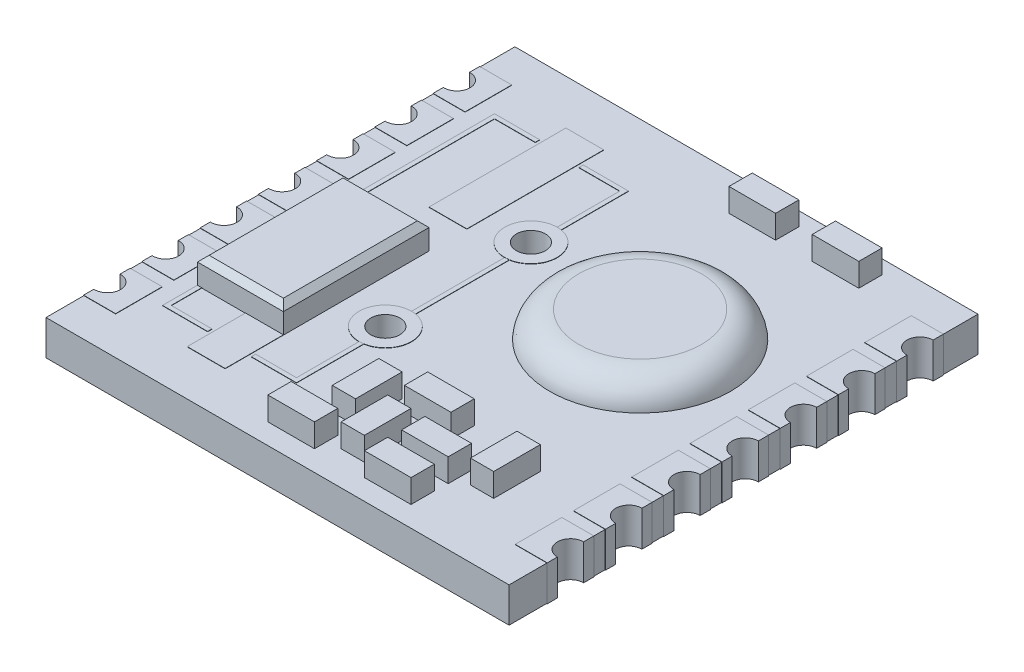
SolidWorks part; units mm, degrees
ref_plane "Vorne" through (0, 0, 0) normal (0, 0, 1) x (1, 0, 0)
ref_plane "Oben" through (0, 0, 0) normal (0, 1, 0) x (1, 0, 0)
ref_plane "Rechts" through (0, 0, 0) normal (1, 0, 0) x (0, 0, -1)
sketch "Skizze1" plane through (0, 0, 0) normal (0, 0, 1) x (1, 0, 0)
  line L1 (0, 0) -> (15.9, 0)
  line L2 (0, 0) -> (0, 1.2)
  line L3 (0, 1.2) -> (15.9, 1.2)
  line L4 (15.9, 0) -> (15.9, 1.2)
  dimension "D1" = 1.2
  dimension "D2" = 15.9
extrude "Linear austragen1" add sketch "Skizze1" along normal blind 16.1
sketch "Skizze3" plane through (15.9, 0, 0) normal (1, 0, 0) x (0, 0, -1)
  line L0 (-16.1, 1.2) -> (0, 1.2) construction
  line L1 (-14.8, 1.2) -> (-13.2, 1.2)
  line L2 (-14.8, 1.2) -> (-14.8, 0)
  line L3 (-14.8, 0) -> (-13.2, 0)
  line L4 (-13.2, 1.2) -> (-13.2, 0)
  line L5 (-16.1, 0) -> (0, 0) construction
  line L6 (-16.1, 0) -> (-16.1, 1.2) construction
  line L7 (-12.8, 1.2) -> (-11.2, 1.2)
  line L8 (-12.8, 1.2) -> (-12.8, 0)
  line L9 (-12.8, 0) -> (-11.2, 0)
  line L10 (-11.2, 1.2) -> (-11.2, 0)
  line L11 (-10.8, 1.2) -> (-9.2, 1.2)
  line L12 (-10.8, 1.2) -> (-10.8, 0)
  line L13 (-10.8, 0) -> (-9.2, 0)
  line L14 (-9.2, 1.2) -> (-9.2, 0)
  line L15 (-8.8, 1.2) -> (-7.2, 1.2)
  line L16 (-8.8, 1.2) -> (-8.8, 0)
  line L17 (-8.8, 0) -> (-7.2, 0)
  line L18 (-7.2, 1.2) -> (-7.2, 0)
  line L19 (-6.8, 1.2) -> (-5.2, 1.2)
  line L20 (-6.8, 1.2) -> (-6.8, 0)
  line L21 (-6.8, 0) -> (-5.2, 0)
  line L22 (-5.2, 1.2) -> (-5.2, 0)
  line L23 (-4.8, 1.2) -> (-3.2, 1.2)
  line L24 (-4.8, 1.2) -> (-4.8, 0)
  line L25 (-4.8, 0) -> (-3.2, 0)
  line L26 (-3.2, 1.2) -> (-3.2, 0)
  line L27 (-2.8, 1.2) -> (-1.2, 1.2)
  line L28 (-2.8, 1.2) -> (-2.8, 0)
  line L29 (-2.8, 0) -> (-1.2, 0)
  line L30 (-1.2, 1.2) -> (-1.2, 0)
  dimension "D1" = 1.6
  dimension "D2" = 1.6
  dimension "D3" = 1.6
  dimension "D4" = 1.3
  dimension "D5" = 0.4
  dimension "D6" = 0.4
  dimension "D7" = 0.4
  dimension "D8" = 0.4
  dimension "D9" = 0.4
  dimension "D10" = 0.4
  dimension "D11" = 1.6
  dimension "D12" = 1.6
  dimension "D13" = 1.6
  dimension "D14" = 1.6
sketch "Skizze4" plane through (0, 0, 0) normal (-1, 0, 0) x (0, 0, 1)
  line L0 (16.1, 1.2) -> (0, 1.2) construction
  line L1 (14.8, 1.2) -> (13.2, 1.2)
  line L2 (14.8, 1.2) -> (14.8, 0)
  line L3 (14.8, 0) -> (13.2, 0)
  line L4 (13.2, 1.2) -> (13.2, 0)
  line L5 (16.1, 0) -> (0, 0) construction
  line L6 (16.1, 1.2) -> (16.1, 0) construction
  line L7 (12.8, 1.2) -> (11.2, 1.2)
  line L8 (12.8, 1.2) -> (12.8, 0)
  line L9 (12.8, 0) -> (11.2, 0)
  line L10 (11.2, 1.2) -> (11.2, 0)
  line L11 (10.8, 1.2) -> (9.2, 1.2)
  line L12 (10.8, 1.2) -> (10.8, 0)
  line L13 (10.8, 0) -> (9.2, 0)
  line L14 (9.2, 1.2) -> (9.2, 0)
  line L15 (8.8, 1.2) -> (7.2, 1.2)
  line L16 (8.8, 1.2) -> (8.8, 0)
  line L17 (8.8, 0) -> (7.2, 0)
  line L18 (7.2, 1.2) -> (7.2, 0)
  line L23 (6.8, 1.2) -> (5.2, 1.2)
  line L24 (6.8, 1.2) -> (6.8, 0)
  line L25 (6.8, 0) -> (5.2, 0)
  line L26 (5.2, 1.2) -> (5.2, 0)
  line L27 (4.8, 1.2) -> (3.2, 1.2)
  line L28 (4.8, 1.2) -> (4.8, 0)
  line L29 (4.8, 0) -> (3.2, 0)
  line L30 (3.2, 1.2) -> (3.2, 0)
  line L31 (2.8, 1.2) -> (1.2, 1.2)
  line L32 (2.8, 1.2) -> (2.8, 0)
  line L33 (2.8, 0) -> (1.2, 0)
  line L34 (1.2, 1.2) -> (1.2, 0)
  dimension "D1" = 0.4
  dimension "D2" = 0.4
  dimension "D3" = 0.4
  dimension "D4" = 0.4
  dimension "D5" = 0.4
  dimension "D6" = 0.4
  dimension "D7" = 1.3
  dimension "D8" = 1.6
  dimension "D9" = 1.6
  dimension "D10" = 1.6
  dimension "D11" = 1.6
  dimension "D12" = 1.6
  dimension "D13" = 1.6
  dimension "D14" = 1.6
extrude "Linear austragen2" add sketch "Skizze4" along normal blind 0.01
extrude "Linear austragen3" add sketch "Skizze3" along normal blind 0.01
sketch "Skizze5" plane through (0, 1.2, 0) normal (0, 1, 0) x (-1, 0, 0)
  line L1 (-15.91, 1.2) -> (-14.81, 1.2)
  line L2 (-15.91, 1.2) -> (-15.91, 2.8)
  line L3 (-15.91, 2.8) -> (-14.81, 2.8)
  line L4 (-14.81, 1.2) -> (-14.81, 2.8)
  line L5 (-15.91, 3.2) -> (-14.81, 3.2)
  line L6 (-15.91, 3.2) -> (-15.91, 4.8)
  line L7 (-15.91, 4.8) -> (-14.81, 4.8)
  line L8 (-14.81, 3.2) -> (-14.81, 4.8)
  line L9 (-15.91, 7.2) -> (-14.81, 7.2)
  line L10 (-15.91, 7.2) -> (-15.91, 8.8)
  line L11 (-15.91, 8.8) -> (-14.81, 8.8)
  line L12 (-14.81, 7.2) -> (-14.81, 8.8)
  line L13 (-15.91, 9.2) -> (-14.81, 9.2)
  line L14 (-15.91, 9.2) -> (-15.91, 10.8)
  line L15 (-15.91, 10.8) -> (-14.81, 10.8)
  line L16 (-14.81, 9.2) -> (-14.81, 10.8)
  line L17 (-15.91, 11.2) -> (-14.81, 11.2)
  line L18 (-15.91, 11.2) -> (-15.91, 12.8)
  line L19 (-15.91, 12.8) -> (-14.81, 12.8)
  line L20 (-14.81, 11.2) -> (-14.81, 12.8)
  line L21 (-15.91, 13.2) -> (-14.81, 13.2)
  line L22 (-15.91, 13.2) -> (-15.91, 14.8)
  line L23 (-15.91, 14.8) -> (-14.81, 14.8)
  line L24 (-14.81, 13.2) -> (-14.81, 14.8)
  line L25 (-15.91, 5.2) -> (-14.81, 5.2)
  line L26 (-15.91, 5.2) -> (-15.91, 6.8)
  line L27 (-15.91, 6.8) -> (-14.81, 6.8)
  line L28 (-14.81, 5.2) -> (-14.81, 6.8)
  line L29 (0.01, 1.2) -> (-1.09, 1.2)
  line L30 (0.01, 1.2) -> (0.01, 2.8)
  line L31 (0.01, 2.8) -> (-1.09, 2.8)
  line L32 (-1.09, 1.2) -> (-1.09, 2.8)
  line L33 (0.01, 3.2) -> (-1.09, 3.2)
  line L34 (0.01, 3.2) -> (0.01, 4.8)
  line L35 (0.01, 4.8) -> (-1.09, 4.8)
  line L36 (-1.09, 3.2) -> (-1.09, 4.8)
  line L37 (0.01, 5.2) -> (-1.09, 5.2)
  line L38 (0.01, 5.2) -> (0.01, 6.8)
  line L39 (0.01, 6.8) -> (-1.09, 6.8)
  line L40 (-1.09, 5.2) -> (-1.09, 6.8)
  line L41 (0.01, 7.2) -> (-1.09, 7.2)
  line L42 (0.01, 7.2) -> (0.01, 8.8)
  line L43 (0.01, 8.8) -> (-1.09, 8.8)
  line L44 (-1.09, 7.2) -> (-1.09, 8.8)
  line L45 (0.01, 9.2) -> (-1.09, 9.2)
  line L46 (0.01, 9.2) -> (0.01, 10.8)
  line L47 (0.01, 10.8) -> (-1.09, 10.8)
  line L48 (-1.09, 9.2) -> (-1.09, 10.8)
  line L49 (0.01, 11.2) -> (-1.09, 11.2)
  line L50 (0.01, 11.2) -> (0.01, 12.8)
  line L51 (0.01, 12.8) -> (-1.09, 12.8)
  line L52 (-1.09, 11.2) -> (-1.09, 12.8)
  line L53 (0.01, 13.2) -> (-1.09, 13.2)
  line L54 (0.01, 13.2) -> (0.01, 14.8)
  line L55 (0.01, 14.8) -> (-1.09, 14.8)
  line L56 (-1.09, 13.2) -> (-1.09, 14.8)
  dimension "D1" = 1.6
  dimension "D2" = 1.6
  dimension "D3" = 1.6
  dimension "D4" = 1.6
  dimension "D5" = 1.6
  dimension "D6" = 1.6
  dimension "D7" = 1.6
  dimension "D8" = 1.1
  dimension "D9" = 1.1
  dimension "D10" = 1.1
  dimension "D11" = 1.1
  dimension "D12" = 1.1
  dimension "D13" = 1.1
  dimension "D14" = 1.1
  dimension "D15" = 1.6
  dimension "D16" = 1.6
  dimension "D17" = 1.6
  dimension "D18" = 1.6
  dimension "D19" = 1.6
  dimension "D20" = 1.6
  dimension "D21" = 1.6
  dimension "D22" = 1.1
  dimension "D23" = 1.1
  dimension "D24" = 1.1
  dimension "D25" = 1.1
  dimension "D26" = 1.1
  dimension "D27" = 1.1
  dimension "D28" = 1.1
extrude "Linear austragen4" add sketch "Skizze5" along normal blind 0.01
sketch "Skizze6" plane through (0, 0, 0) normal (0, -1, 0) x (1, 0, 0)
  line L1 (15.91, 14.8) -> (14.81, 14.8)
  line L2 (15.91, 14.8) -> (15.91, 13.2)
  line L3 (15.91, 13.2) -> (14.81, 13.2)
  line L4 (14.81, 14.8) -> (14.81, 13.2)
  line L5 (15.91, 12.8) -> (14.81, 12.8)
  line L6 (15.91, 12.8) -> (15.91, 11.2)
  line L7 (15.91, 11.2) -> (14.81, 11.2)
  line L8 (14.81, 12.8) -> (14.81, 11.2)
  line L9 (15.91, 10.8) -> (14.81, 10.8)
  line L10 (15.91, 10.8) -> (15.91, 9.2)
  line L11 (15.91, 9.2) -> (14.81, 9.2)
  line L12 (14.81, 10.8) -> (14.81, 9.2)
  line L13 (15.91, 8.8) -> (14.81, 8.8)
  line L14 (15.91, 8.8) -> (15.91, 7.2)
  line L15 (15.91, 7.2) -> (14.81, 7.2)
  line L16 (14.81, 8.8) -> (14.81, 7.2)
  line L17 (15.91, 6.8) -> (14.81, 6.8)
  line L18 (15.91, 6.8) -> (15.91, 5.2)
  line L19 (15.91, 5.2) -> (14.81, 5.2)
  line L20 (14.81, 6.8) -> (14.81, 5.2)
  line L21 (15.91, 4.8) -> (14.81, 4.8)
  line L22 (15.91, 4.8) -> (15.91, 3.2)
  line L23 (15.91, 3.2) -> (14.81, 3.2)
  line L24 (14.81, 4.8) -> (14.81, 3.2)
  line L25 (15.91, 2.8) -> (14.81, 2.8)
  line L26 (15.91, 2.8) -> (15.91, 1.2)
  line L27 (15.91, 1.2) -> (14.81, 1.2)
  line L28 (14.81, 2.8) -> (14.81, 1.2)
  line L29 (-0.01, 14.8) -> (1.09, 14.8)
  line L30 (-0.01, 14.8) -> (-0.01, 13.2)
  line L31 (-0.01, 13.2) -> (1.09, 13.2)
  line L32 (1.09, 14.8) -> (1.09, 13.2)
  line L33 (-0.01, 12.8) -> (1.09, 12.8)
  line L34 (-0.01, 12.8) -> (-0.01, 11.2)
  line L35 (-0.01, 11.2) -> (1.09, 11.2)
  line L36 (1.09, 12.8) -> (1.09, 11.2)
  line L37 (-0.01, 10.8) -> (1.09, 10.8)
  line L38 (-0.01, 10.8) -> (-0.01, 9.2)
  line L39 (-0.01, 9.2) -> (1.09, 9.2)
  line L40 (1.09, 10.8) -> (1.09, 9.2)
  line L41 (-0.01, 8.8) -> (1.09, 8.8)
  line L42 (-0.01, 8.8) -> (-0.01, 7.2)
  line L43 (-0.01, 7.2) -> (1.09, 7.2)
  line L44 (1.09, 8.8) -> (1.09, 7.2)
  line L45 (-0.01, 6.8) -> (1.09, 6.8)
  line L46 (-0.01, 6.8) -> (-0.01, 5.2)
  line L47 (-0.01, 5.2) -> (1.09, 5.2)
  line L48 (1.09, 6.8) -> (1.09, 5.2)
  line L49 (-0.01, 4.8) -> (1.09, 4.8)
  line L50 (-0.01, 4.8) -> (-0.01, 3.2)
  line L51 (-0.01, 3.2) -> (1.09, 3.2)
  line L52 (1.09, 4.8) -> (1.09, 3.2)
  line L53 (-0.01, 2.8) -> (1.09, 2.8)
  line L54 (-0.01, 2.8) -> (-0.01, 1.2)
  line L55 (-0.01, 1.2) -> (1.09, 1.2)
  line L56 (1.09, 2.8) -> (1.09, 1.2)
  dimension "D1" = 1.6
  dimension "D2" = 1.6
  dimension "D3" = 1.6
  dimension "D4" = 1.6
  dimension "D5" = 1.6
  dimension "D6" = 1.6
  dimension "D7" = 1.6
  dimension "D8" = 1.1
  dimension "D9" = 1.1
  dimension "D10" = 1.1
  dimension "D11" = 1.1
  dimension "D12" = 1.1
  dimension "D13" = 1.1
  dimension "D14" = 1.1
  dimension "D15" = 1.6
  dimension "D16" = 1.6
  dimension "D17" = 1.6
  dimension "D18" = 1.6
  dimension "D19" = 1.6
  dimension "D20" = 1.6
  dimension "D21" = 1.6
  dimension "D22" = 1.1
  dimension "D23" = 1.1
  dimension "D24" = 1.1
  dimension "D25" = 1.1
  dimension "D26" = 1.1
  dimension "D27" = 1.1
  dimension "D28" = 1.1
extrude "Linear austragen5" add sketch "Skizze6" along normal blind 0.01
sketch "Skizze7" plane through (0, 1.21, 0) normal (0, 1, 0) x (-1, 0, 0)
  line L0 (-15.91, 2.8) -> (-15.91, 1.2) construction
  line L1 (-15.91, 1.2) -> (-14.81, 1.2) construction
  line L2 (-15.91, 2) -> (-0.01, 2) construction
  line L3 (-15.91, 2) -> (-15.91, 4) construction
  circle A0 centre (-15.91, 2) radius 0.45
  circle A1 centre (-0.01, 2) radius 0.45
  circle A2 centre (-15.91, 4) radius 0.45
  circle A3 centre (-0.01, 4) radius 0.45
  circle A4 centre (-15.91, 6) radius 0.45
  circle A5 centre (-0.01, 6) radius 0.45
  circle A6 centre (-15.91, 8) radius 0.45
  circle A7 centre (-0.01, 8) radius 0.45
  circle A8 centre (-15.91, 10) radius 0.45
  circle A9 centre (-0.01, 10) radius 0.45
  circle A10 centre (-15.91, 12) radius 0.45
  circle A11 centre (-0.01, 12) radius 0.45
  circle A12 centre (-15.91, 14) radius 0.45
  circle A13 centre (-0.01, 14) radius 0.45
  dimension "D2" = 0.9
  dimension "D1" = 0.8
  dimension "D3" = 90
extrude "Schnitt-Linear austragen2" cut sketch "Skizze7" against normal blind 2
sketch "Skizze8" plane through (0, 1.2, 0) normal (0, 1, 0) x (-1, 0, 0)
  line L0 (-15.9, 5.2) -> (-15.9, 4.8) construction
  line L1 (-15.9, 0) -> (0, 0) construction
  circle A0 centre (-10.85, 6.55) radius 3.1
  dimension "D2" = 6.2
  dimension "D1" = 5.05
  dimension "D3" = 6.55
extrude "Linear austragen6" add sketch "Skizze8" along normal blind 0.9
fillet "Verrundung1" radius 1 1 edges at (7.75, 2.1, 6.55)
sketch "Skizze9" plane through (0, 1.2, 0) normal (0, 1, 0) x (-1, 0, 0)
  line L0 (0, 1.2) -> (0, 0) construction
  line L1 (-1.65, 2.35) -> (-3.2, 2.35)
  line L2 (-1.65, 2.35) -> (-1.65, 13.75)
  line L3 (-1.65, 13.75) -> (-3.2, 13.75)
  line L4 (-6.25, 2.35) -> (-6.25, 13.75)
  line L5 (-15.9, 0) -> (0, 0) construction
  line L6 (-3.2, 2.35) -> (-3.2, 2.5)
  line L7 (-1.8, 2.5) -> (-3.2, 2.5)
  line L8 (-1.8, 2.5) -> (-1.8, 13.6)
  line L9 (-1.8, 13.6) -> (-3.2, 13.6)
  line L10 (-6.1, 2.5) -> (-6.1, 13.6)
  line L11 (-4.7, 2.35) -> (-4.7, 2.5)
  line L12 (-4.7, 2.35) -> (-6.25, 2.35)
  line L13 (-4.7, 2.5) -> (-6.1, 2.5)
  line L14 (-3.2, 13.6) -> (-3.2, 13.75)
  line L15 (-4.7, 13.6) -> (-4.7, 13.75)
  line L16 (-4.7, 13.6) -> (-6.1, 13.6)
  line L17 (-4.7, 13.75) -> (-6.25, 13.75)
  dimension "D1" = 4.6
  dimension "D2" = 11.4
  dimension "D3" = 6.25
  dimension "D4" = 2.35
  dimension "D5" = 0.15
  dimension "D6" = 0.15
  dimension "D7" = 0.15
  dimension "D8" = 0.15
  dimension "D9" = 1.55
  dimension "D10" = 1.55
extrude "Linear austragen7" add sketch "Skizze9" along normal blind 0.01
sketch "Skizze10" plane through (0, 1.2, 0) normal (0, 1, 0) x (-1, 0, 0)
  line L0 (-6.1, 2.5) -> (-6.1, 13.6) construction
  line L1 (-15.9, 0) -> (0, 0) construction
  circle A0 centre (-6.1, 5.55) radius 0.9
  circle A1 centre (-6.1, 10.55) radius 0.9
  dimension "D3" = 1.8
  dimension "D4" = 1.8
  dimension "D1" = 5
  dimension "D2" = 5.55
extrude "Linear austragen9" add sketch "Skizze10" along normal blind 0.011
sketch "Skizze11" plane through (0, 1.211, 0) normal (0, 1, 0) x (-1, 0, 0)
  circle A0 centre (-6.1, 10.55) radius 0.5
  circle A1 centre (-6.1, 5.55) radius 0.5
  dimension "D1" = 1
  dimension "D2" = 1
extrude "Schnitt-Linear austragen3" cut sketch "Skizze11" against normal blind 2
sketch "Skizze12" plane through (0, 1.2, 0) normal (0, 1, 0) x (-1, 0, 0)
  line L1 (-3.3, 1.55) -> (-4.6, 1.55)
  line L2 (-3.3, 1.55) -> (-3.3, 6.25)
  line L3 (-3.3, 14.55) -> (-4.6, 14.55)
  line L4 (-4.6, 1.55) -> (-4.6, 6.25)
  line L5 (-4.7, 2.35) -> (-4.7, 2.5) construction
  line L6 (-6.25, 2.35) -> (-4.7, 2.35) construction
  line L7 (-4.7, 13.75) -> (-6.25, 13.75) construction
  line L8 (-3.3, 6.25) -> (-4.6, 6.25)
  line L9 (-3.3, 9.85) -> (-4.6, 9.85)
  line L10 (-4.6, 9.85) -> (-4.6, 14.55)
  line L11 (-3.3, 9.85) -> (-3.3, 14.55)
  dimension "D1" = 1.3
  dimension "D2" = 0.1
  dimension "D3" = 0.8
  dimension "D4" = 0.8
  dimension "D5" = 4.7
  dimension "D6" = 4.7
extrude "Linear austragen10" add sketch "Skizze12" along normal blind 0.01
sketch "Skizze13" plane through (0, 1.2, 0) normal (0, 1, 0) x (-1, 0, 0)
  line L0 (-1.65, 2.35) -> (-1.65, 13.75) construction
  line L1 (-1.65, 7.55) -> (-4.6, 7.55)
  line L2 (-1.65, 7.55) -> (-1.65, 12.55)
  line L3 (-1.65, 12.55) -> (-4.6, 12.55)
  line L4 (-4.6, 7.55) -> (-4.6, 12.55)
  line L5 (-4.6, 14.55) -> (-4.6, 9.85) construction
  line L6 (-3.3, 6.25) -> (-4.6, 6.25) construction
  dimension "D1" = 1.3
  dimension "D2" = 5
extrude "Linear austragen11" add sketch "Skizze13" along normal blind 0.9
chamfer "Fase1" distance 0.2 angle 45 4 edges at (1.65, 2.1, 10.05) (3.125, 2.1, 12.55) (3.125, 2.1, 7.55) (4.6, 2.1, 10.05)
sketch "Skizze14" plane through (0, 1.2, 0) normal (0, 1, 0) x (-1, 0, 0)
  line L0 (-11.4841, 0.4772) -> (-13.0841, 0.4772)
  line L1 (-8.6266, 0.4772) -> (-10.2266, 0.4772)
  line L2 (-8.6266, 0.4772) -> (-8.6266, 1.2772)
  line L3 (-8.6266, 1.2772) -> (-10.2266, 1.2772)
  line L4 (-10.2266, 0.4772) -> (-10.2266, 1.2772)
  line L5 (-11.4841, 0.4772) -> (-11.4841, 1.2772)
  line L6 (-11.4841, 1.2772) -> (-13.0841, 1.2772)
  line L7 (-13.0841, 0.4772) -> (-13.0841, 1.2772)
  line L8 (-10.2267, 14.594) -> (-11.8267, 14.594)
  line L9 (-10.2267, 14.594) -> (-10.2267, 15.394)
  line L10 (-10.2267, 15.394) -> (-11.8267, 15.394)
  line L11 (-11.8267, 14.594) -> (-11.8267, 15.394)
  line L12 (-10.2458, 13.3367) -> (-11.8458, 13.3367)
  line L13 (-10.2458, 13.3367) -> (-10.2458, 14.1367)
  line L14 (-10.2458, 14.1367) -> (-11.8458, 14.1367)
  line L15 (-11.8458, 13.3367) -> (-11.8458, 14.1367)
  line L16 (-8.9694, 11.965) -> (-10.5694, 11.965)
  line L17 (-8.9694, 11.965) -> (-8.9694, 12.765)
  line L18 (-8.9694, 12.765) -> (-10.5694, 12.765)
  line L19 (-10.5694, 11.965) -> (-10.5694, 12.765)
  line L20 (-6.9119, 14.594) -> (-8.5119, 14.594)
  line L21 (-6.9119, 14.594) -> (-6.9119, 15.394)
  line L22 (-6.9119, 15.394) -> (-8.5119, 15.394)
  line L23 (-8.5119, 14.594) -> (-8.5119, 15.394)
  line L24 (-8.9692, 13.3367) -> (-9.7692, 13.3367)
  line L25 (-8.9692, 13.3367) -> (-8.9692, 14.9367)
  line L26 (-8.9692, 14.9367) -> (-9.7692, 14.9367)
  line L27 (-9.7692, 13.3367) -> (-9.7692, 14.9367)
  line L28 (-7.731, 12.4032) -> (-8.531, 12.4032)
  line L29 (-7.731, 12.4032) -> (-7.731, 14.0032)
  line L30 (-7.731, 14.0032) -> (-8.531, 14.0032)
  line L31 (-8.531, 12.4032) -> (-8.531, 14.0032)
  line L32 (-12.2651, 12.1936) -> (-13.0651, 12.1936)
  line L33 (-12.2651, 12.1936) -> (-12.2651, 13.7936)
  line L34 (-12.2651, 13.7936) -> (-13.0651, 13.7936)
  line L35 (-13.0651, 12.1936) -> (-13.0651, 13.7936)
  dimension "D1" = 1.6
  dimension "D2" = 0.8
  dimension "D3" = 1.6
  dimension "D4" = 0.8
  dimension "D5" = 1.6
  dimension "D6" = 1.6
extrude "Linear austragen12" add sketch "Skizze14" along normal blind 0.8
